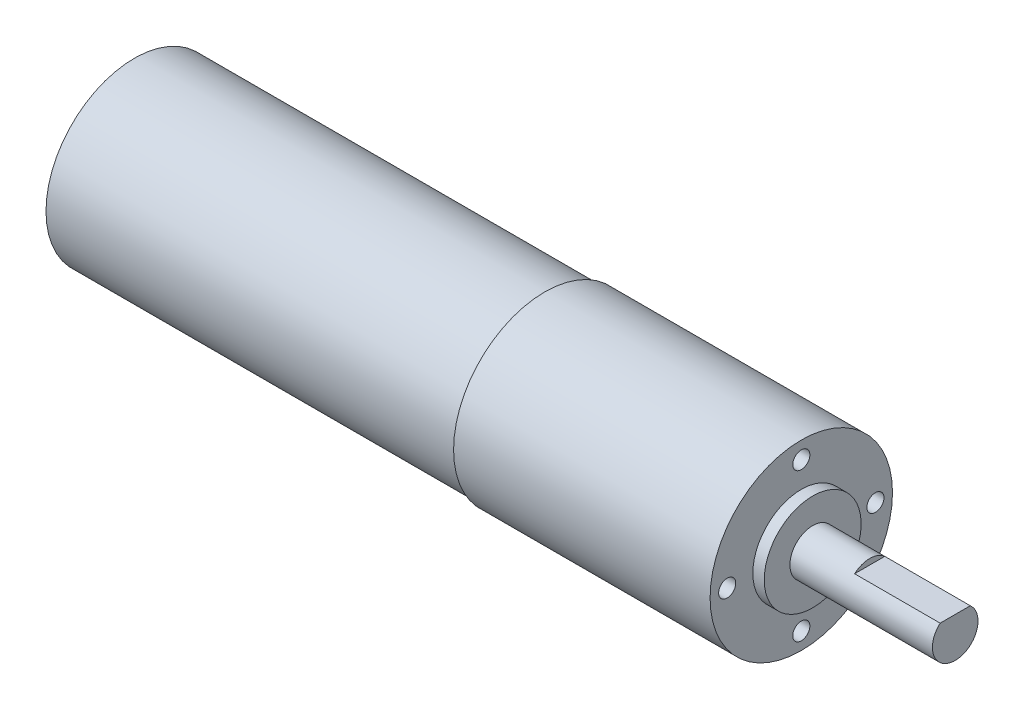
SolidWorks part; units mm, degrees
ref_plane "Front Plane" through (0, 0, 0) normal (0, 0, 1) x (1, 0, 0)
ref_plane "Top Plane" through (0, 0, 0) normal (0, 1, 0) x (1, 0, 0)
ref_plane "Right Plane" through (0, 0, 0) normal (1, 0, 0) x (0, 0, -1)
sketch "Sketch1" plane through (0, 0, 0) normal (0, 0, 1) x (1, 0, 0)
  line L0 (0, 0) -> (0, 15.5)
  line L1 (0, 15.5) -> (72, 15.5)
  line L2 (72, 15.5) -> (72, 16)
  line L3 (72, 16) -> (117, 16)
  line L4 (117, 16) -> (117, 8.5)
  line L5 (117, 8.5) -> (119, 8.5)
  line L6 (119, 8.5) -> (119, 4)
  line L7 (119, 4) -> (144, 4)
  line L8 (144, 4) -> (144, 0)
  line L9 (0, 0) -> (144, 0) construction
  line L10 (0, 0) -> (144, 0)
  dimension "D1" = 31
  dimension "D2" = 32
  dimension "D3" = 72
  dimension "D4" = 45
  dimension "D5" = 17
  dimension "D6" = 8
  dimension "D7" = 2
  dimension "D8" = 25
revolve "Revolve1" add sketch "Sketch1" angle 360 about L9
sketch "Sketch2" plane through (144, 0, 0) normal (1, 0, 0) x (0, 0, -1)
  line L0 (-2.6458, 3) -> (2.6458, 3)
  arc A0 (2.6458, 3) -> (-2.6458, 3) centre (0, 0) ccw
  circle A1 centre (0, 0) radius 4 construction
  dimension "D1" = 3
extrude "Cut-Extrude1" cut sketch "Sketch2" against normal blind 15
sketch "Sketch3" plane through (117, 0, 0) normal (1, 0, 0) x (0, 0, -1)
  circle A0 centre (0, 0) radius 13 construction
  circle A1 centre (0, 13) radius 1.5
  circle A3 centre (13, 0) radius 1.5
  circle A4 centre (0, -13) radius 1.5
  circle A5 centre (-13, 0) radius 1.5
  point P14 (0, 0)
  dimension "D1" = 26
  dimension "D2" = 3
  dimension "D3" = 4
extrude "Cut-Extrude2" cut sketch "Sketch3" against normal blind 5
